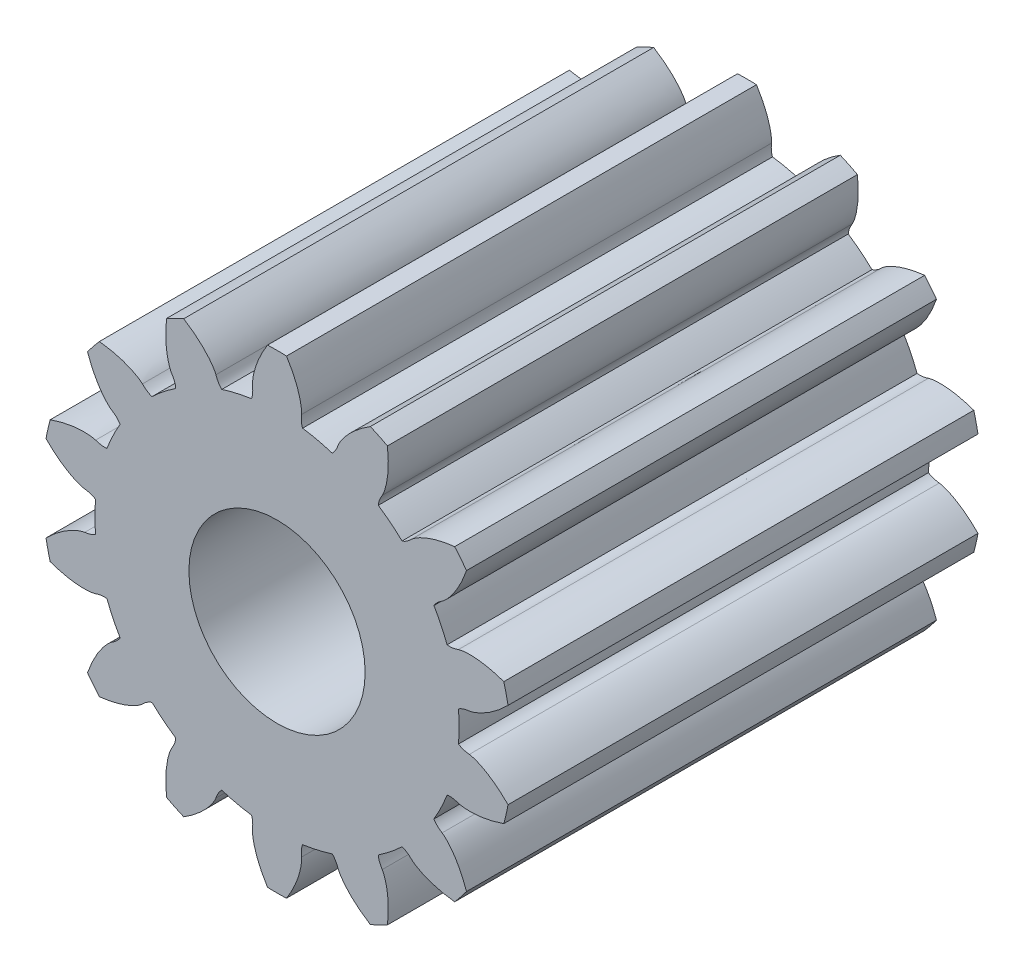
SolidWorks part; units mm, degrees
note: '?' marks a value the reader was unsure of.
ref_plane "정면" through (0, 0, 0) normal (0, 0, 1) x (1, 0, 0)
ref_plane "윗면" through (0, 0, 0) normal (0, 1, 0) x (1, 0, 0)
ref_plane "우측면" through (0, 0, 0) normal (1, 0, 0) x (0, 0, -1)
ref_axis "축1" through (0, 0, -88.99) along (0, 0, 1)?
sketch "스케치1" plane through (0, 0, 0) normal (0, 0, 1) x (1, 0, 0)
  circle A0 centre (0, 0) radius 1.55
extrude "돌출1" add sketch "스케치1" along normal blind 4
sketch "스케치2" plane through (0, 0, 0) normal (0, 0, -1) x (-1, 0, 0)
  arc A0 (-0.0807, 1.9984) -> (0.0807, 1.9984) centre (0, 0)
  arc A1 (-0.2895, 1.4718) -> (0.2895, 1.4718) centre (0, 0)
  spline S0 degree 3 poles (-0.2085, 1.6312) (-0.2086, 1.6336) (-0.2093, 1.6423) (-0.2087, 1.6614) (-0.2056, 1.6924) (-0.1976, 1.7349) (-0.1829, 1.7882) (-0.1594, 1.8514) (-0.1259, 1.9235) (-0.0965, 1.9723) (-0.0807, 1.9984) knots 0 0 0 0 0.017884 0.066372 0.145464 0.255161 0.395464 0.566371 0.767883 1 1 1 1
  spline S1 degree 3 poles (0.2085, 1.6312) (0.2086, 1.6336) (0.2093, 1.6423) (0.2087, 1.6614) (0.2056, 1.6924) (0.1976, 1.7349) (0.1829, 1.7882) (0.1594, 1.8514) (0.1259, 1.9235) (0.0965, 1.9723) (0.0807, 1.9984) knots 0 0 0 0 0.017884 0.066372 0.145464 0.255161 0.395464 0.566371 0.767883 1 1 1 1
  spline S2 degree 3 poles (-0.2085, 1.6312) (-0.2077, 1.6238) (-0.2063, 1.6091) (-0.2064, 1.5873) (-0.2085, 1.5661) (-0.2133, 1.5449) (-0.2218, 1.5233) (-0.2361, 1.5017) (-0.2585, 1.4814) (-0.2787, 1.4751) (-0.2895, 1.4718) knots 0 0 0 0 0.114365 0.223817 0.33066 0.43847 0.552749 0.681182 0.83107 1 1 1 1
  spline S3 degree 3 poles (0.2085, 1.6312) (0.2077, 1.6238) (0.2063, 1.6091) (0.2064, 1.5873) (0.2085, 1.5661) (0.2133, 1.5449) (0.2218, 1.5233) (0.2361, 1.5017) (0.2585, 1.4814) (0.2787, 1.4751) (0.2895, 1.4718) knots 0 0 0 0 0.114365 0.223817 0.33066 0.43847 0.552749 0.681182 0.83107 1 1 1 1
extrude "돌출2" add sketch "스케치2" against normal blind 4
pattern_circular "원형 패턴1" count 14 every 25.714 about axis through (0, 0, -88.99) along (0, 0, 1) of "돌출2"
sketch "스케치3" plane through (0, 0, 4) normal (0, 0, 1) x (1, 0, 0)
  circle A0 centre (0, 0) radius 0.75
extrude "컷-돌출1" cut sketch "스케치3" against normal through all
